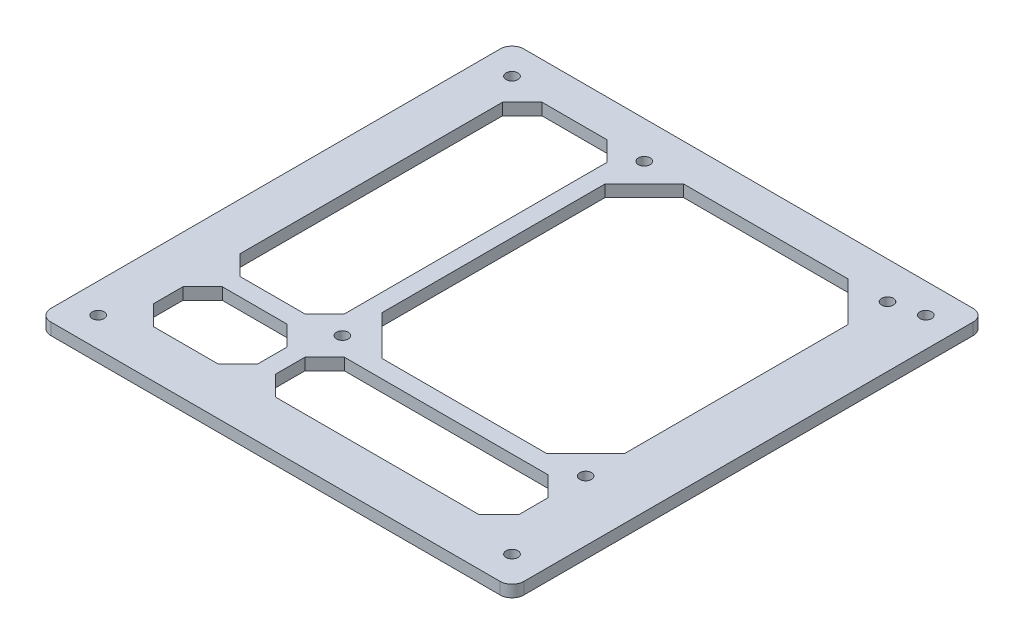
SolidWorks part; units mm, degrees
ref_plane "前基準面" through (0, 0, 0) normal (0, 0, 1) x (1, 0, 0)
ref_plane "上基準面" through (0, 0, 0) normal (0, 1, 0) x (1, 0, 0)
ref_plane "右基準面" through (0, 0, 0) normal (1, 0, 0) x (0, 0, -1)
sketch "草圖1" plane through (0, 0, 0) normal (0, 1, 0) x (1, 0, 0)
  line L0 (-52.5, 52.5) -> (52.5, 52.5) construction
  line L1 (-60, 60) -> (60, 60)
  line L2 (-60, 60) -> (-60, -60)
  line L3 (-60, -60) -> (60, -60)
  line L4 (60, 60) -> (60, -60)
  line L5 (-60, 60) -> (60, -60) construction
  line L6 (-60, -60) -> (60, 60) construction
  line L7 (-52.5, 52.5) -> (-52.5, -52.5) construction
  line L8 (-52.5, 52.5) -> (-52.5, 60) construction
  line L9 (-52.5, 52.5) -> (-60, 52.5) construction
  circle A0 centre (-52.5, 52.5) radius 1.5
  circle A1 centre (52.5, 52.5) radius 1.5
  circle A2 centre (52.5, -52.5) radius 1.5
  circle A3 centre (-52.5, -52.5) radius 1.5
  point P0 (0, 0)
  dimension "D7" = 3
  dimension "D1" = 120
  dimension "D2" = 120
  dimension "D5" = 105
  dimension "D6" = 105
  dimension "D8" = 7.5
  dimension "D3" = 2
  dimension "D4" = 2
extrude "填料-伸長1" add sketch "草圖1" along normal blind 3
sketch "草圖2" plane through (0, 3, 0) normal (0, 1, 0) x (1, 0, 0)
  line L0 (0, 0) -> (55.2066, 0) construction
  line L1 (55.2066, 0) -> (-60.768, 0) construction
  line L2 (0, 0) -> (0, 56.6444) construction
  line L3 (0, 56.6444) -> (0, -55.3423) construction
  line L5 (-48.75, 48.75) -> (48.75, 48.75)
  line L6 (-48.75, 48.75) -> (-48.75, -48.75)
  line L7 (-48.75, -48.75) -> (48.75, -48.75)
  line L8 (48.75, 48.75) -> (48.75, -48.75)
  line L9 (-48.75, 48.75) -> (48.75, -48.75) construction
  line L10 (-48.75, -48.75) -> (48.75, 48.75) construction
  dimension "D1" = 97.5
  dimension "D2" = 97.5
sketch "草圖3" plane through (0, 3, 0) normal (0, 1, 0) x (1, 0, 0)
  line L0 (48.75, 48.75) -> (48.75, -48.75) construction
  line L1 (-21.1, 64.6) -> (48.75, 64.6)
  line L2 (-21.1, 64.6) -> (-21.1, -35.85)
  line L3 (-21.1, -35.85) -> (48.75, -35.85)
  line L4 (48.75, 64.6) -> (48.75, -35.85)
  line L5 (-21.1, 60) -> (48.75, 60)
  line L6 (60, 60) -> (-60, 60) construction
  line L7 (-17.035, 50.6) -> (44.685, 50.6) construction
  line L8 (-17.035, 50.6) -> (-17.035, -26) construction
  line L9 (-17.035, 50.6) -> (-21.1, 50.6) construction
  line L10 (44.685, 50.6) -> (48.75, 50.6) construction
  point P10 (-17.035, 50.6)
  point P14 (44.685, 50.6)
  point P15 (44.685, -26)
  point P16 (-17.035, -26)
  dimension "D1" = 69.85
  dimension "D2" = 100.45
  dimension "D3" = 4.6
  dimension "D7" = 61.72
  dimension "D8" = 76.6
  dimension "D9" = 9.4
  dimension "D5" = 2
  dimension "D6" = 2
sketch "草圖4" plane through (0, 3, 0) normal (0, 1, 0) x (1, 0, 0)
  line L0 (-17.035, 40.6) -> (-7.035, 50.6)
  line L1 (-7.035, 50.6) -> (34.685, 50.6)
  line L2 (-17.035, 40.6) -> (-17.035, -16)
  line L3 (-7.035, -26) -> (34.685, -26)
  line L4 (44.685, 40.6) -> (44.685, -16)
  line L5 (34.685, 50.6) -> (44.685, 40.6)
  line L6 (34.685, -26) -> (44.685, -16)
  line L7 (-17.035, -16) -> (-7.035, -26)
  point P0 (-17.035, 50.6)
  point P1 (44.685, -26)
  point P2 (-17.035, -26)
  point P3 (44.685, 50.6)
hole_wizard "Ø3.0mm 定位孔1" positions "3D草圖1" profile "草圖5" hole size "Ø3.0" standard "GB" end condition through all
sketch3d "3D草圖1"
  point P0 (-17.035, 3, -50.6)
  point P3 (44.685, 3, -50.6)
  point P6 (44.685, 3, 26)
  point P9 (-17.035, 3, 26)
sketch "草圖5" plane through (-17.035, 3, -50.6) normal (1, 0, 0) x (0, 0, 1)
  line L0 (0, 0) -> (0, 3)
  line L1 (0, 3) -> (1.5, 3)
  line L2 (1.5, 3) -> (1.5, 0)
  line L5 (1.5, 0) -> (0, 0)
  line L11 (0, -6.35) -> (0, 107.95) construction
  dimension "貫穿孔直徑" = 3
  dimension "貫穿孔深度" = 3
extrude "除料-伸長1" cut sketch "草圖4" against normal through all
sketch "草圖6" plane through (0, 3, 0) normal (0, 1, 0) x (1, 0, 0)
  line L0 (44.685, -16) -> (44.685, 40.6) construction
  line L1 (-48, 50.6) -> (-21.535, 50.6)
  line L2 (-48, 50.6) -> (-48, -26)
  line L3 (-48, -26) -> (-21.535, -26)
  line L4 (-21.535, 50.6) -> (-21.535, -26)
  line L5 (-17.035, -30.5) -> (44.685, -30.5)
  line L6 (-17.035, -30.5) -> (-17.035, -48)
  line L7 (-17.035, -48) -> (44.685, -48)
  line L8 (44.685, -30.5) -> (44.685, -48)
  line L9 (-17.035, 40.6) -> (-17.035, -16) construction
  line L10 (34.685, 50.6) -> (-7.035, 50.6) construction
  line L11 (-7.035, -26) -> (34.685, -26) construction
  line L13 (-48, -30.5) -> (-21.535, -30.5)
  line L14 (-48, -30.5) -> (-48, -48)
  line L15 (-48, -48) -> (-21.535, -48)
  line L16 (-21.535, -30.5) -> (-21.535, -48)
  circle A0 centre (44.685, -26) radius 1.5 construction
  circle A1 centre (-17.035, 50.6) radius 1.5 construction
  circle A2 centre (-52.5, 52.5) radius 1.5 construction
  circle A3 centre (52.5, -52.5) radius 1.5 construction
  dimension "D2" = 4.5
  dimension "D1" = 4.5
  dimension "D3" = 4.5
  dimension "D4" = 4.5
extrude "除料-伸長2" cut sketch "草圖6" against normal through all
chamfer "導角1" distance 5 angle 45 12 edges at (-17.035, 1.5, 48) (44.685, 1.5, 48) (44.685, 1.5, 30.5) (-17.035, 1.5, 30.5) (-21.535, 1.5, 48) (-48, 1.5, 48) (-48, 1.5, 30.5) (-21.535, 1.5, 30.5) (-48, 1.5, 26) (-21.535, 1.5, 26) (-48, 1.5, -50.6) (-21.535, 1.5, -50.6)
fillet "圓角1" radius 3 4 edges at (-60, 1.5, 60) (60, 1.5, 60) (60, 1.5, -60) (-60, 1.5, -60)
